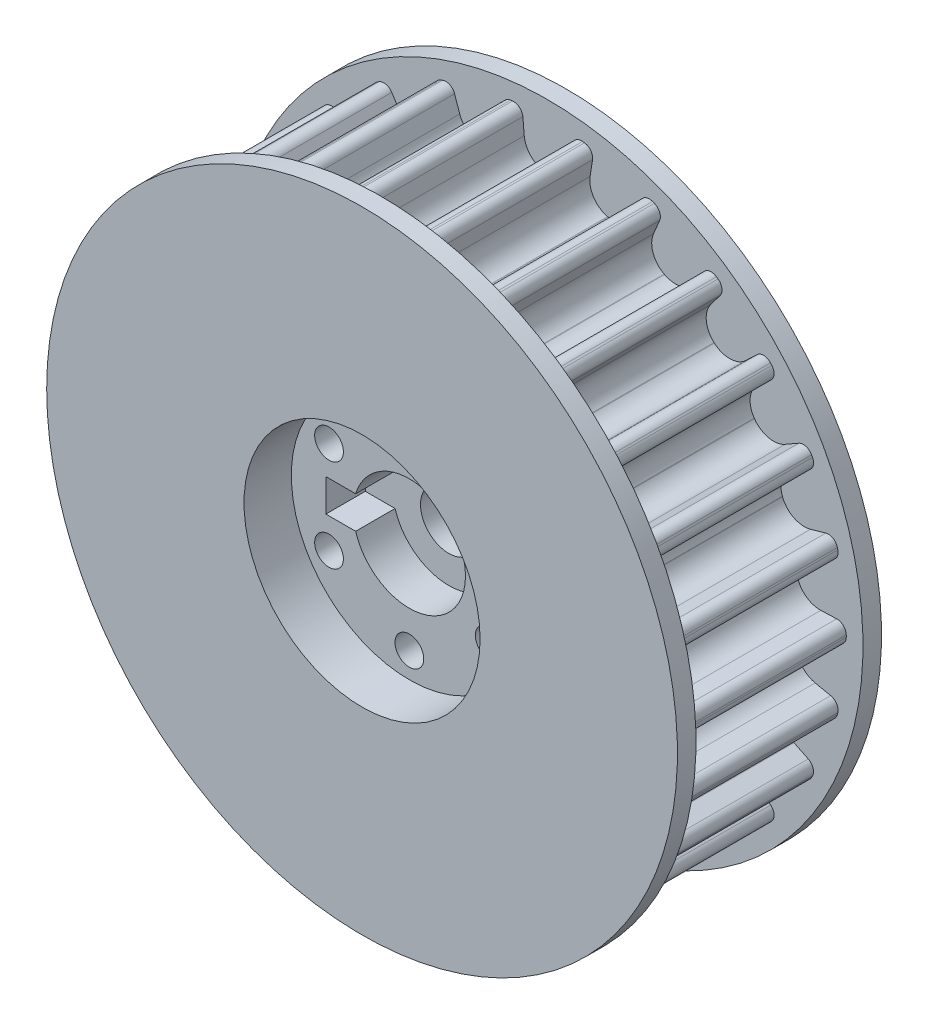
SolidWorks part; units mm, degrees
ref_plane "Front Plane" through (0, 0, 0) normal (0, 0, 1) x (1, 0, 0)
ref_plane "Top Plane" through (0, 0, 0) normal (0, 1, 0) x (1, 0, 0)
ref_plane "Right Plane" through (0, 0, 0) normal (1, 0, 0) x (0, 0, -1)
sketch "Sketch1" plane through (0, 0, 0) normal (0, 0, 1) x (1, 0, 0)
  circle A0 centre (0, 0) radius 32.2
  dimension "D1" = 64.4
extrude "Boss-Extrude1" add sketch "Sketch1" along normal mid plane 18
sketch "Sketch2" plane through (0, 0, 9) normal (0, 0, 1) x (1, 0, 0)
  line L0 (-2.75, 32.0824) -> (-2.3214, 27.0824)
  line L1 (-2.3214, 27.0824) -> (2.3214, 27.0824)
  line L2 (0, -55) -> (0, 55) construction
  line L3 (0, 0) -> (-2.75, 32.0824) construction
  line L4 (2.75, 32.0824) -> (2.3214, 27.0824)
  circle A0 centre (0, 0) radius 32.2 construction
  arc A1 (-2.75, 32.0824) -> (2.75, 32.0824) centre (0, 32.3181) cw
  point P8 (0, 27.0824)
  dimension "D1" = 5
  dimension "D2" = 5.5
extrude "Cut-Extrude2" cut sketch "Sketch2" against normal up to next
fillet "Fillet1" radius 2.5 2 edges at (2.3214, 27.0824, 0) (-2.3214, 27.0824, 0)
fillet "Fillet2" radius 1 2 edges at (2.75, 32.0824, 0) (-2.75, 32.0824, 0)
ref_axis "Axis1" through (0, 0, -7.7129) along (0, 0, 1)
pattern_circular "CirPattern1" count 26 over 360 about axis through (0, 0, -7.7129) along (0, 0, 1) of "Fillet1", "Cut-Extrude2", "Fillet2"
sketch "Sketch3" plane through (0, 0, -9) normal (0, 0, -1) x (-1, 0, 0)
  circle A0 centre (0, 0) radius 34
  dimension "D1" = 68
extrude "Boss-Extrude2" add sketch "Sketch3" along normal blind 2
mirror "Mirror1" about plane through (0, 0, 0) normal (0, 0, 1) of "Boss-Extrude2"
ref_plane "Plane1" through (0, 0, 11) normal (0, 0, 1) x (1, 0, 0)
sketch "Sketch4" plane through (0, 0, 11) normal (0, 0, 1) x (1, 0, 0)
  circle A0 centre (0, 0) radius 12.725
  dimension "D1" = 25.45
extrude "Cut-Extrude3" cut sketch "Sketch4" against normal blind 5.1
sketch "Sketch5" plane through (0, 0, 11) normal (0, 0, 1) x (1, 0, 0)
  circle A0 centre (0, 0) radius 6.05
  dimension "D1" = 12.1
extrude "Cut-Extrude4" cut sketch "Sketch5" against normal blind 9.35
sketch "Sketch6" plane through (0, 0, 11) normal (0, 0, 1) x (1, 0, 0)
  circle A0 centre (0, 0) radius 3.05
  dimension "D1" = 6.1
extrude "Cut-Extrude5" cut sketch "Sketch6" against normal through all
sketch "Sketch7" plane through (0, 0, 11) normal (0, 0, 1) x (1, 0, 0)
  line L0 (0, -12.1) -> (0, 12.1) construction
  circle A1 centre (0, 10) radius 1.55
  dimension "D1" = 3.1
  dimension "D2" = 10
extrude "Cut-Extrude6" cut sketch "Sketch7" against normal through all
pattern_circular "CirPattern2" count 6 over 360 about axis through (0, 0, -7.7129) along (0, 0, 1) of "Cut-Extrude6"
sketch "Sketch8" plane through (0, 0, 11) normal (0, 0, 1) x (1, 0, 0)
  line L1 (-9, 1.75) -> (0, 1.75)
  line L2 (-9, 1.75) -> (-9, -1.75)
  line L3 (-9, -1.75) -> (0, -1.75)
  line L4 (0, 1.75) -> (0, -1.75)
  line L5 (-36.2768, 0) -> (39.0302, 0) construction
  line L6 (0, -12.1) -> (0, 12.1) construction
  dimension "D1" = 3.5
  dimension "D2" = 9
extrude "Cut-Extrude7" cut sketch "Sketch8" against normal up to surface (9.35 mm away) up to face at (3.05, 0, 1.65)
